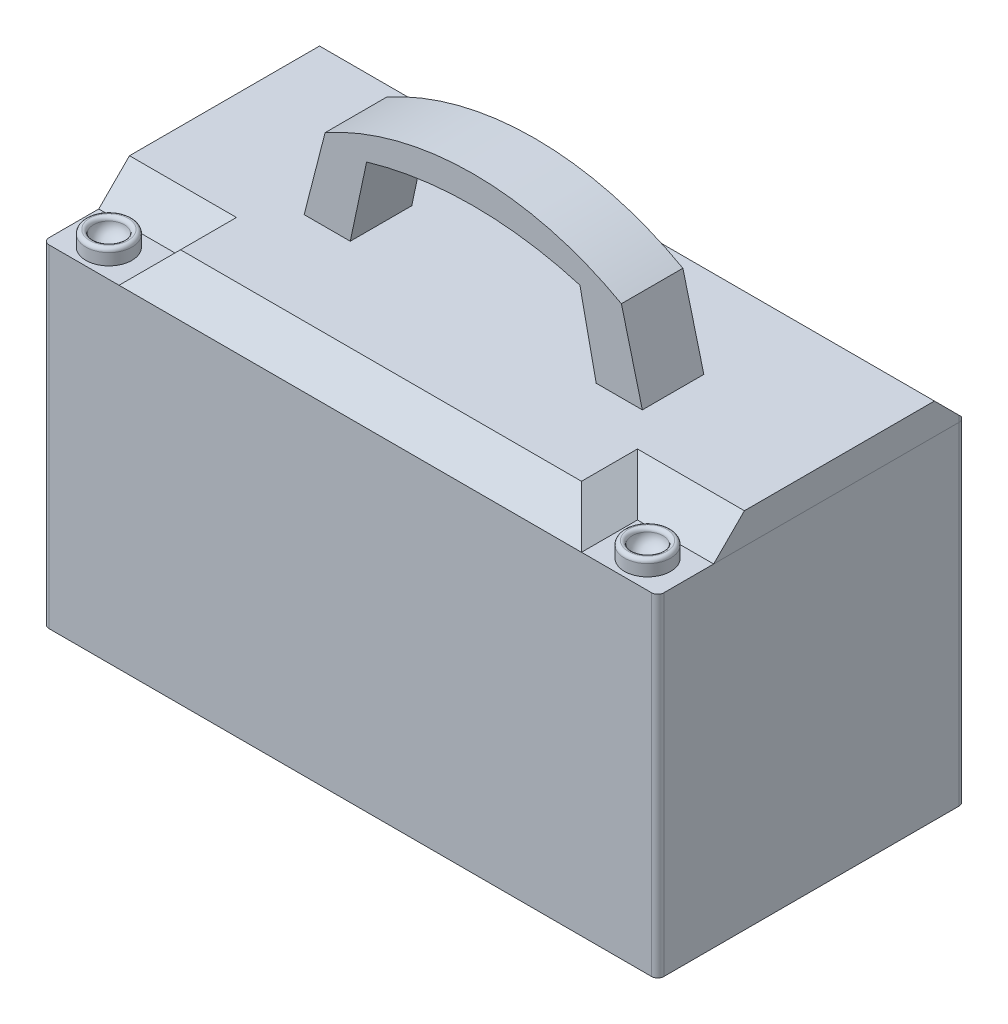
SolidWorks part; units mm, degrees
ref_plane "Front Plane" through (0, 0, 0) normal (0, 0, 1) x (1, 0, 0)
ref_plane "Top Plane" through (0, 0, 0) normal (0, 1, 0) x (1, 0, 0)
ref_plane "Right Plane" through (0, 0, 0) normal (1, 0, 0) x (0, 0, -1)
sketch "Sketch1" plane through (0, 0, 0) normal (0, 1, 0) x (1, 0, 0)
  line L1 (0, 0) -> (254, 0)
  line L2 (0, 0) -> (0, 127)
  line L3 (0, 127) -> (254, 127)
  line L4 (254, 0) -> (254, 127)
  dimension "D1" = 127
  dimension "D2" = 254
extrude "Boss-Extrude1" add sketch "Sketch1" along normal blind 150
sketch "Sketch2" plane through (0, 150, 0) normal (0, 1, 0) x (1, 0, 0)
  line L0 (127, 127) -> (127, 0) construction
  line L1 (0, 0) -> (31.4832, 0)
  line L2 (0, 0) -> (0, 23.1067)
  line L3 (0, 23.1067) -> (31.4832, 23.1067)
  line L4 (31.4832, 0) -> (31.4832, 23.1067)
  line L5 (254, 127) -> (0, 127) construction
  line L6 (0, 0) -> (254, 0) construction
extrude "Cut-Extrude1" cut sketch "Sketch2" against normal blind 12.7 contours L2 L1 L4 L3
sketch "Sketch3" plane through (0, 137.3, 0) normal (0, 1, 0) x (1, 0, 0)
  line L0 (15.7416, 23.1067) -> (15.7416, 0) construction
  line L1 (31.4832, 23.1067) -> (0, 23.1067) construction
  line L3 (31.4832, 11.5534) -> (0, 11.5534) construction
  line L6 (31.4832, 0) -> (31.4832, 23.1067) construction
  line L7 (0, 0) -> (0, 23.1067) construction
  line L8 (0, 0) -> (31.4832, 0) construction
  circle A0 centre (15.7416, 11.5534) radius 6.35
  circle A1 centre (15.7416, 11.5534) radius 9.525
  dimension "D1" = 12.7
  dimension "D2" = 19.05
extrude "Boss-Extrude2" add sketch "Sketch3" along normal blind 6.35
fillet "Fillet1" radius 1.5875 2 edges at (15.7416, 143.65, -5.2034) (15.7416, 143.65, -2.0284)
ref_plane "Plane1" through (127, 0, 0) normal (1, 0, 0) x (0, 0, -1)
mirror "Mirror1" about plane through (127, 0, 0) normal (1, 0, 0) of "Cut-Extrude1", "Boss-Extrude2", "Fillet1"
chamfer "Chamfer1" distance 12.7 angle 45 6 edges at (31.4832, 150, -11.5534) (15.7416, 150, -23.1067) (127, 150, -127) (238.2584, 150, -23.1067) (222.5168, 150, -11.5534) (127, 150, 0)
fillet "Fillet2" radius 5.08 2 edges at (238.2584, 137.3, -5.2034) (15.7416, 137.3, -5.2034)
fillet "Fillet3" radius 2.54 4 edges at (0, 68.65, 0) (0, 68.65, -127) (254, 68.65, -127) (254, 68.65, 0)
sketch "Sketch4" plane through (0, 0, 0) normal (0, 0, 1) x (1, 0, 0)
  line L0 (127, 137.3) -> (127, 262.3194) construction
  line L1 (177.8, 150) -> (196.85, 150)
  line L2 (44.1832, 150) -> (209.8168, 150) construction
  line L3 (196.85, 150) -> (188.1963, 183.655)
  line L4 (177.8, 150) -> (171.0513, 181.75)
  line L8 (222.5168, 137.3) -> (31.4832, 137.3) construction
  line L9 (127, 188.1) -> (112.8739, 188.1) construction
  line L10 (127, 199.53) -> (114.1427, 199.53) construction
  line L11 (57.15, 150) -> (65.8037, 183.655)
  line L12 (76.2, 150) -> (57.15, 150)
  line L13 (76.2, 150) -> (82.9487, 181.75)
  arc A4 (171.0513, 181.75) -> (82.9487, 181.75) centre (127, 32.1282) ccw
  arc A5 (188.1963, 183.655) -> (65.8037, 183.655) centre (127, 73.64) ccw
  dimension "D1" = 19.05
  dimension "D2" = 1.905
  dimension "D3" = 17.145
  dimension "D4" = 78
  dimension "D5" = 50.8
  dimension "D6" = 38.1
  dimension "D7" = 31.75
  dimension "D8" = 11.43
extrude "Boss-Extrude3" add sketch "Sketch4" against normal blind 25.4 from offset 50.8 offset against normal yes
sketch "Sketch6" plane through (254, 0, 0) normal (1, 0, 0) x (0, 0, -1)
  line L0 (23.1067, 137.3) -> (127, 137.3)
  line L1 (127, 137.3) -> (127, 0) construction
split line "Split Line1"
ref_plane "Plane2" through (127, 0, -127) normal (-0.7071, 0, 0.7071) x (0.7071, 0, 0.7071)
ref_plane "Plane3" through (197.5666, 0, -197.5666) normal (-0.7071, 0, 0.7071) x (0.7071, 0, 0.7071)
sketch "Sketch7" plane through (197.5666, 0, -197.5666) normal (-0.7071, 0, 0.7071) x (0.7071, 0, 0.7071)
  line L0 (91.5986, 137.3) -> (88.0065, 137.3)
curve "Curve1"
split line "Split Line2"
sketch "Sketch7<3>" plane through (197.5666, 0, -197.5666) normal (-0.7071, 0, 0.7071) x (0.7071, 0, 0.7071) same geometry as "Sketch7"
sketch "Sketch8" plane through (0, 0, 0) normal (-1, 0, 0) x (0, 0, 1)
  line L0 (-23.1067, 137.3) -> (-127, 137.3)
split line "Split Line3"
ref_plane "Plane4" through (0, 0, 0) normal (-0.7071, 0, -0.7071) x (-0.7071, 0, 0.7071)
ref_plane "Plane5" through (-67.0456, 0, -67.0456) normal (-0.7071, 0, -0.7071) x (-0.7071, 0, 0.7071)
sketch "Sketch9" plane through (-67.0456, 0, -67.0456) normal (-0.7071, 0, -0.7071) x (-0.7071, 0, 0.7071)
  line L0 (-88.0065, 137.3) -> (-91.5986, 137.3)
split line "Split Line4"
